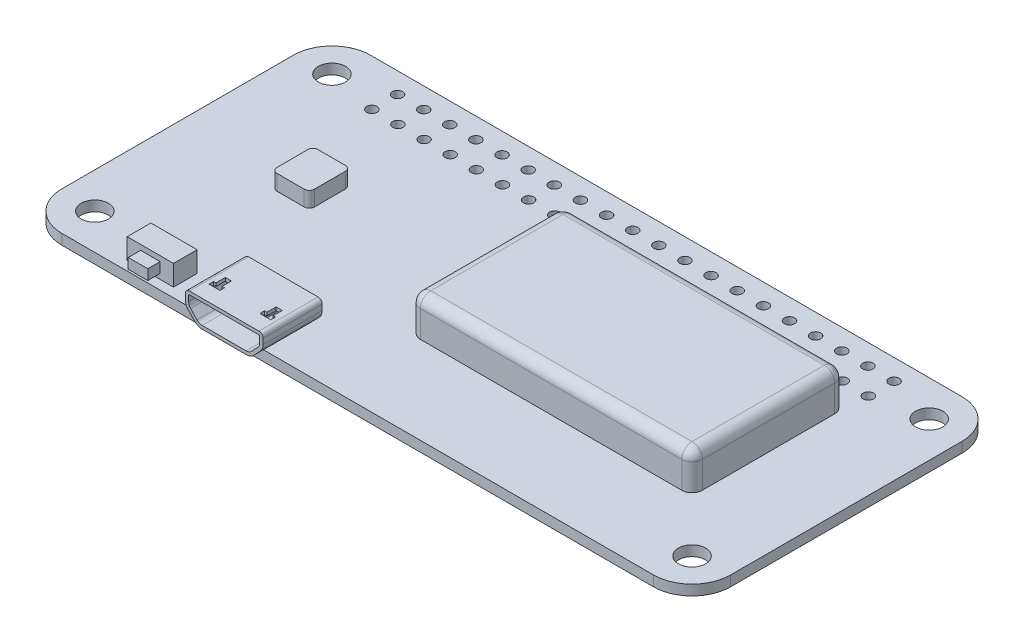
SolidWorks part; units mm, degrees
ref_plane "Front Plane" through (0, 0, 0) normal (0, 0, 1) x (1, 0, 0)
ref_plane "Top Plane" through (0, 0, 0) normal (0, 1, 0) x (1, 0, 0)
ref_plane "Right Plane" through (0, 0, 0) normal (1, 0, 0) x (0, 0, -1)
sketch "Sketch1" plane through (0, 0, 0) normal (0, 1, 0) x (1, 0, 0)
  line L1 (-28.75, 15) -> (28.75, 15)
  line L2 (-32.5, 11.25) -> (-32.5, -11.25)
  line L3 (-28.75, -15) -> (28.75, -15)
  line L4 (32.5, 11.25) -> (32.5, -11.25)
  line L5 (-32.5, 15) -> (32.5, -15) construction
  line L6 (-32.5, -15) -> (32.5, 15) construction
  arc A0 (-32.5, -11.25) -> (-28.75, -15) centre (-28.75, -11.25) ccw
  arc A1 (28.75, -15) -> (32.5, -11.25) centre (28.75, -11.25) ccw
  arc A2 (28.75, 15) -> (32.5, 11.25) centre (28.75, 11.25) cw
  arc A3 (-28.75, 15) -> (-32.5, 11.25) centre (-28.75, 11.25) ccw
  point P0 (0, 0)
  dimension "D3" = 3.75
  dimension "D1" = 65
  dimension "D2" = 30
extrude "Boss-Extrude1" add sketch "Sketch1" along normal blind 1 contours L1 A2 L4 A1 L3 A0 L2 A3
sketch "Sketch2" plane through (0, 1, 0) normal (0, 1, 0) x (1, 0, 0)
  line L0 (0, 15) -> (0, -15) construction
  line L1 (-28.75, 15) -> (28.75, 15) construction
  line L2 (-28.75, -15) -> (28.75, -15) construction
  line L3 (-32.5, 0) -> (32.5, 0) construction
  line L4 (-32.5, 11.25) -> (-32.5, -11.25) construction
  line L5 (32.5, 11.25) -> (32.5, -11.25) construction
  circle A0 centre (-29.025, 11.525) radius 1.325
  circle A2 centre (29.025, 11.525) radius 1.325
  circle A3 centre (29.025, -11.525) radius 1.325
  circle A4 centre (-29.025, -11.525) radius 1.325
  dimension "D1" = 2.65
  dimension "D2" = 2.15
  dimension "D3" = 2.15
extrude "Cut-Extrude1" cut sketch "Sketch2" against normal through all
sketch "Sketch3" plane through (0, 1, 0) normal (0, 1, 0) x (1, 0, 0)
  line L0 (-24.128, 13) -> (-24.128, 10.5) construction
  line L3 (-28.75, 15) -> (28.75, 15) construction
  line L5 (-32.5, 11.25) -> (-32.5, -11.25) construction
  circle A0 centre (-24.128, 13) radius 0.5
  circle A1 centre (-24.128, 10.5) radius 0.5
  dimension "D1" = 1
  dimension "D3" = 1.5
  dimension "D4" = 7.872
  dimension "D2" = 2.5
extrude "Cut-Extrude2" cut sketch "Sketch3" against normal through all
pattern_linear "LPattern1" count 20 spacing 2.54 along (1, 0, 0) of "Cut-Extrude2"
sketch "Sketch6" plane through (0, 1, 0) normal (0, 1, 0) x (1, 0, 0)
  line L0 (-28.75, -15) -> (28.75, -15) construction
  line L1 (-3.4, 8.35) -> (24, 8.35)
  line L2 (-3.4, 8.35) -> (-3.4, -6.5)
  line L3 (-3.4, -6.5) -> (24, -6.5)
  line L4 (24, 8.35) -> (24, -6.5)
  line L5 (-3.4, 8.35) -> (24, -6.5) construction
  line L6 (-3.4, -6.5) -> (24, 8.35) construction
  line L8 (32.5, 11.25) -> (32.5, -11.25) construction
  point P0 (10.3, 0.925)
  dimension "D1" = 27.4
  dimension "D2" = 8.5
  dimension "D3" = 8.5
  dimension "D4" = 14.85
sketch "Sketch15" plane through (0, 0, 15) normal (0, 0, 1) x (1, 0, 0)
  line L0 (-11.725, 1) -> (-11.725, 3.6) construction
  line L1 (-28.75, 1) -> (28.75, 1) construction
  line L2 (-15.1, 3.6) -> (-8.35, 3.6)
  line L3 (-7.95, 3.2) -> (-7.95, 2.6523)
  line L4 (-8.2286, 1.9598) -> (-8.8548, 1.3075)
  line L5 (-9.5762, 1) -> (-13.8738, 1)
  line L7 (-15.2214, 1.9598) -> (-14.5952, 1.3075)
  line L8 (-15.5, 3.2) -> (-15.5, 2.6523)
  line L9 (-32.5, 1) -> (-32.5, 0) construction
  arc A0 (-8.8548, 1.3075) -> (-9.5762, 1) centre (-9.5762, 2) cw
  arc A1 (-14.5952, 1.3075) -> (-13.8738, 1) centre (-13.8738, 2) ccw
  arc A2 (-7.95, 2.6523) -> (-8.2286, 1.9598) centre (-8.95, 2.6523) cw
  arc A3 (-15.2214, 1.9598) -> (-15.5, 2.6523) centre (-14.5, 2.6523) cw
  arc A4 (-8.35, 3.6) -> (-7.95, 3.2) centre (-8.35, 3.2) cw
  arc A5 (-15.5, 3.2) -> (-15.1, 3.6) centre (-15.1, 3.2) cw
  point P14 (-9.15, 1)
  point P17 (-14.3, 1)
  point P20 (-7.95, 2.25)
  point P23 (-15.5, 2.25)
  point P26 (-7.95, 3.6)
  point P29 (-15.5, 3.6)
  point P30 (-15.5, 2.9262)
  dimension "D6" = 1
  dimension "D7" = 0.4
  dimension "D1" = 7.55
  dimension "D2" = 2.6
  dimension "D3" = 1.35
  dimension "D4" = 5.15
  dimension "D5" = 17
extrude "Boss-Extrude6" add sketch "Sketch15" along normal blind 1.25 and the other way blind 4.5
sketch "Sketch16" plane through (0, 0, 16.25) normal (0, 0, 1) x (1, 0, 0)
  line L30 (-9.0857, 1.5291) -> (-8.4595, 2.1814)
  line L31 (-8.27, 2.6523) -> (-8.27, 3.2)
  line L32 (-8.35, 3.28) -> (-15.1, 3.28)
  line L33 (-15.18, 3.2) -> (-15.18, 2.6523)
  line L34 (-14.9905, 2.1814) -> (-14.3643, 1.5291)
  line L35 (-13.8738, 1.32) -> (-9.5762, 1.32)
  line L36 (-9.0857, 1.5291) -> (-8.4595, 2.1814)
  line L37 (-8.27, 2.6523) -> (-8.27, 3.2)
  line L38 (-8.35, 3.28) -> (-15.1, 3.28)
  line L39 (-15.18, 3.2) -> (-15.18, 2.6523)
  line L40 (-14.9905, 2.1814) -> (-14.3643, 1.5291)
  line L41 (-13.8738, 1.32) -> (-9.5762, 1.32)
  arc A30 (-9.5762, 1.32) -> (-9.0857, 1.5291) centre (-9.5762, 2) ccw
  arc A31 (-8.4595, 2.1814) -> (-8.27, 2.6523) centre (-8.95, 2.6523) ccw
  arc A32 (-8.27, 3.2) -> (-8.35, 3.28) centre (-8.35, 3.2) ccw
  arc A33 (-15.1, 3.28) -> (-15.18, 3.2) centre (-15.1, 3.2) ccw
  arc A34 (-15.18, 2.6523) -> (-14.9905, 2.1814) centre (-14.5, 2.6523) ccw
  arc A35 (-14.3643, 1.5291) -> (-13.8738, 1.32) centre (-13.8738, 2) ccw
  arc A36 (-9.5762, 1.32) -> (-9.0857, 1.5291) centre (-9.5762, 2) ccw
  arc A37 (-8.4595, 2.1814) -> (-8.27, 2.6523) centre (-8.95, 2.6523) ccw
  arc A38 (-8.27, 3.2) -> (-8.35, 3.28) centre (-8.35, 3.2) ccw
  arc A39 (-15.1, 3.28) -> (-15.18, 3.2) centre (-15.1, 3.2) ccw
  arc A40 (-15.18, 2.6523) -> (-14.9905, 2.1814) centre (-14.5, 2.6523) ccw
  arc A41 (-14.3643, 1.5291) -> (-13.8738, 1.32) centre (-13.8738, 2) ccw
  dimension "D2" = 0.32
extrude "Cut-Extrude9" cut sketch "Sketch16" against normal blind 5.25
sketch "Sketch17" plane through (0, 0, 11) normal (0, 0, 1) x (1, 0, 0)
  line L15 (-11.725, 1.32) -> (-11.725, 3.28) construction
  line L16 (-13.8738, 1.32) -> (-9.5762, 1.32) construction
  line L17 (-8.35, 3.28) -> (-15.1, 3.28) construction
  line L19 (-13.3, 2.52) -> (-10.15, 2.52)
  line L20 (-13.3, 2.52) -> (-13.3, 2.92)
  line L21 (-13.3, 2.92) -> (-10.15, 2.92)
  line L22 (-10.15, 2.52) -> (-10.15, 2.92)
  line L23 (-13.3, 2.52) -> (-10.15, 2.92) construction
  line L24 (-13.3, 2.92) -> (-10.15, 2.52) construction
  point P29 (-11.725, 2.72)
  dimension "D4" = 1.4
  dimension "D5" = 0.4
  dimension "D6" = 3.15
extrude "Boss-Extrude7" add sketch "Sketch17" along normal blind 3.5
sketch "Sketch18" plane through (0, 3.6, 0) normal (0, 1, 0) x (1, 0, 0)
  line L0 (-14.5, -13.37) -> (-14.5, -14.27)
  line L1 (-9.25, -13.37) -> (-9.25, -14.72) construction
  line L2 (-9.55, -13.37) -> (-9.55, -14.27)
  line L3 (-9.55, -14.27) -> (-9.775, -14.27)
  line L4 (-9.775, -14.27) -> (-9.775, -14.72)
  line L5 (-8.725, -14.27) -> (-8.725, -14.72)
  line L6 (-8.95, -14.27) -> (-8.725, -14.27)
  line L7 (-8.725, -14.72) -> (-9.775, -14.72)
  line L8 (-9.55, -13.37) -> (-8.95, -13.37)
  line L9 (-8.95, -13.37) -> (-8.95, -14.27)
  line L23 (-14.2, -13.37) -> (-14.2, -14.72) construction
  line L25 (-11.725, -16.25) -> (-11.725, -10.5) construction
  line L26 (-13.9, -13.37) -> (-14.5, -13.37)
  line L30 (-14.725, -14.72) -> (-13.675, -14.72)
  line L34 (-14.5, -14.27) -> (-14.725, -14.27)
  line L35 (-14.725, -14.27) -> (-14.725, -14.72)
  line L36 (-13.675, -14.27) -> (-13.675, -14.72)
  line L37 (-13.9, -14.27) -> (-13.675, -14.27)
  line L38 (-13.9, -13.37) -> (-13.9, -14.27)
  line L43 (-8.35, -16.25) -> (-15.1, -16.25) construction
  line L44 (-8.35, -10.5) -> (-15.1, -10.5) construction
  point P0 (0, 0)
  point P77 (-11.725, -16.25)
  point P80 (-11.725, -10.5)
  point P83 (-14.2, -14.72)
  point P85 (-14.2, -13.37)
  dimension "D7" = 1.53
  dimension "D8" = 1.05
  dimension "D9" = 0.6
  dimension "D10" = 1.35
  dimension "D11" = 0.9
  dimension "D13" = 2.475
extrude "Cut-Extrude10" cut sketch "Sketch18" against normal up to next
sketch "Sketch22" plane through (0, 1, 0) normal (0, 1, 0) x (1, 0, 0)
  line L1 (-22.35, 3) -> (-18.7, 3)
  line L2 (-22.35, 3) -> (-22.35, -1)
  line L3 (-22.35, -1) -> (-18.7, -1)
  line L4 (-18.7, 3) -> (-18.7, -1)
  line L5 (-28.75, 15) -> (28.75, 15) construction
  line L6 (-32.5, 11.25) -> (-32.5, -11.25) construction
  point P4 (-18.7, 1)
  dimension "D1" = 3.65
  dimension "D2" = 4
  dimension "D3" = 13.8
  dimension "D4" = 12
extrude "Boss-Extrude11" add sketch "Sketch22" along normal blind 1.5
fillet "Fillet5" radius 0.5 4 edges at (-18.7, 1.75, -3) (-22.35, 1.75, -3) (-18.7, 1.75, 1) (-22.35, 1.75, 1)
extrude "Boss-Extrude12" add sketch "Sketch6" along normal blind 3.6
fillet "Fillet4" radius 1 8 edges at (-3.4, 4.6, -0.925) (10.3, 4.6, 6.5) (24, 4.6, -0.925) (10.3, 4.6, -8.35) (-3.4, 2.8, -8.35) (24, 2.8, -8.35) (-3.4, 2.8, 6.5) (24, 2.8, 6.5)
sketch "Sketch23" plane through (0, 1, 0) normal (0, 1, 0) x (1, 0, 0)
  line L0 (-15.5, -10.5) -> (-15.5, -16.25) construction
  line L1 (-23.3, -11.8) -> (-18.8, -11.8)
  line L2 (-23.3, -11.8) -> (-23.3, -14.1)
  line L3 (-23.3, -14.1) -> (-18.8, -14.1)
  line L4 (-18.8, -11.8) -> (-18.8, -14.1)
  line L7 (-28.75, -15) -> (-13.8738, -15) construction
  dimension "D1" = 4.5
  dimension "D2" = 2.3
  dimension "D3" = 3.3
  dimension "D4" = 3.2
extrude "Boss-Extrude13" add sketch "Sketch23" along normal blind 2
sketch "Sketch24" plane through (0, 0, 14.1) normal (0, 0, 1) x (1, 0, 0)
  line L0 (-21.05, 3) -> (-21.05, 1) construction
  line L1 (-23.3, 3) -> (-18.8, 3) construction
  line L2 (-23.3, 1) -> (-18.8, 1) construction
  line L4 (-22, 2.5) -> (-20.1, 2.5)
  line L5 (-22, 2.5) -> (-22, 1.5)
  line L6 (-22, 1.5) -> (-20.1, 1.5)
  line L7 (-20.1, 2.5) -> (-20.1, 1.5)
  line L8 (-22, 2.5) -> (-20.1, 1.5) construction
  line L9 (-22, 1.5) -> (-20.1, 2.5) construction
  point P6 (-21.05, 2)
  point P11 (-22, 2)
  dimension "D1" = 1.9
  dimension "D2" = 1
extrude "Boss-Extrude14" add sketch "Sketch24" along normal blind 1.2
sketch "Sketch25" plane through (0, 0, 0) normal (0, -1, 0) x (1, 0, 0)
  line L0 (-28.75, 15) -> (28.75, 15) construction
  line L1 (-22.4, 12.1) -> (-19.1, 12.1)
  line L2 (-22.4, 12.1) -> (-22.4, 11.17)
  line L3 (-22.4, 11.17) -> (-19.1, 11.17)
  line L4 (-19.1, 12.1) -> (-19.1, 11.17)
  line L5 (-22.4, 9.6) -> (-19.1, 9.6)
  line L6 (-22.4, 9.6) -> (-22.4, 8.67)
  line L7 (-22.4, 8.67) -> (-19.1, 8.67)
  line L8 (-19.1, 9.6) -> (-19.1, 8.67)
  line L9 (-32.5, -11.25) -> (-32.5, 11.25) construction
  point P10 (-22.4, 9.135)
  dimension "D1" = 2.9
  dimension "D2" = 3.43
  dimension "D3" = 3.3
  dimension "D4" = 10.1
  dimension "D5" = 0.93
extrude "Boss-Extrude15" add sketch "Sketch25" along normal blind 1
fillet "Fillet6" radius 0.5 2 edges at (-19.1, -1, 9.135) (-19.1, -1, 11.635)
sketch "Sketch26" plane through (0, -1, 0) normal (0, -1, 0) x (1, 0, 0)
  line L0 (-22.4, 11.17) -> (-19.6, 11.17) construction
  line L1 (-22.1, 11.17) -> (-21.2, 11.17)
  line L2 (-22.1, 11.17) -> (-22.1, 12.1)
  line L3 (-22.1, 12.1) -> (-21.2, 12.1)
  line L4 (-21.2, 11.17) -> (-21.2, 12.1)
  line L5 (-19.6, 12.1) -> (-22.4, 12.1) construction
  line L6 (-22.4, 8.67) -> (-19.6, 8.67) construction
  line L7 (-22.1, 8.67) -> (-21.2, 8.67)
  line L8 (-22.1, 8.67) -> (-22.1, 9.6)
  line L9 (-22.1, 9.6) -> (-21.2, 9.6)
  line L10 (-21.2, 8.67) -> (-21.2, 9.6)
  line L11 (-19.6, 9.6) -> (-22.4, 9.6) construction
  line L12 (-22.4, 12.1) -> (-22.4, 11.17) construction
  dimension "D1" = 0.9
  dimension "D2" = 0.3
extrude "Boss-Extrude16" add sketch "Sketch26" along normal blind 0.7
fillet "Fillet7" radius 0.5 4 edges at (-22.1, -1.7, 11.635) (-21.2, -1.7, 11.635) (-22.1, -1.7, 9.135) (-21.2, -1.7, 9.135)
sketch "Sketch27" plane through (0, 0, 0) normal (0, -1, 0) x (1, 0, 0)
  line L0 (-29.5, 6.75) -> (-29.5, -6.75) construction
  line L1 (-30.5, 7.4) -> (-28.5, 7.4)
  line L2 (-30.5, 7.4) -> (-30.5, 6.1)
  line L3 (-30.5, 6.1) -> (-28.5, 6.1)
  line L4 (-28.5, 7.4) -> (-28.5, 6.1)
  line L5 (-30.5, 7.4) -> (-28.5, 6.1) construction
  line L6 (-30.5, 6.1) -> (-28.5, 7.4) construction
  line L7 (-30.5, 2.9) -> (-28.5, 2.9)
  line L8 (-30.5, 2.9) -> (-30.5, 1.6)
  line L9 (-30.5, 1.6) -> (-28.5, 1.6)
  line L10 (-28.5, 2.9) -> (-28.5, 1.6)
  line L11 (-30.5, 2.9) -> (-28.5, 1.6) construction
  line L12 (-30.5, 1.6) -> (-28.5, 2.9) construction
  line L13 (-30.5, -1.6) -> (-28.5, -1.6)
  line L14 (-30.5, -1.6) -> (-30.5, -2.9)
  line L15 (-30.5, -2.9) -> (-28.5, -2.9)
  line L16 (-28.5, -1.6) -> (-28.5, -2.9)
  line L17 (-30.5, -1.6) -> (-28.5, -2.9) construction
  line L18 (-30.5, -2.9) -> (-28.5, -1.6) construction
  line L19 (-30.5, -6.1) -> (-28.5, -6.1)
  line L20 (-30.5, -6.1) -> (-30.5, -7.4)
  line L21 (-30.5, -7.4) -> (-28.5, -7.4)
  line L22 (-28.5, -6.1) -> (-28.5, -7.4)
  line L23 (-30.5, -6.1) -> (-28.5, -7.4) construction
  line L24 (-30.5, -7.4) -> (-28.5, -6.1) construction
  line L25 (-29.5, 15) -> (-29.5, -15) construction
  line L26 (-28.75, 15) -> (28.75, 15) construction
  line L27 (-28.75, -15) -> (28.75, -15) construction
  line L28 (-32.5, -11.25) -> (-32.5, 11.25) construction
  point P0 (-29.5, 6.75)
  point P5 (-29.5, 2.25)
  point P10 (-29.5, -2.25)
  point P15 (-29.5, -6.75)
  point P22 (-29.5, 0)
  point P23 (-29.5, 0)
  point P24 (-25.596, -15)
  dimension "D1" = 13.5
  dimension "D2" = 1.3
  dimension "D3" = 4.5
  dimension "D4" = 4.5
  dimension "D5" = 2
  dimension "D6" = 4
extrude "Boss-Extrude17" add sketch "Sketch27" along normal blind 0.2
sketch "Sketch28" plane through (0, -0.2, 0) normal (0, -1, 0) x (1, 0, 0)
  line L0 (-29.5, 7.4) -> (-29.5, -7.4) construction
  line L1 (-28.5, 7.4) -> (-30.5, 7.4) construction
  line L2 (-30.5, -7.4) -> (-28.5, -7.4) construction
  line L3 (-28.5, 2.9) -> (-30.5, 2.9) construction
  line L4 (-28.9, 6.1) -> (-30.1, 6.1)
  line L5 (-28.9, 6.1) -> (-28.9, 7.4)
  line L6 (-28.9, 7.4) -> (-30.1, 7.4)
  line L7 (-30.1, 6.1) -> (-30.1, 7.4)
  line L8 (-28.9, 6.1) -> (-30.1, 7.4) construction
  line L9 (-28.9, 7.4) -> (-30.1, 6.1) construction
  line L10 (-28.9, 1.6) -> (-30.1, 1.6)
  line L11 (-28.9, 1.6) -> (-28.9, 2.9)
  line L12 (-28.9, 2.9) -> (-30.1, 2.9)
  line L13 (-30.1, 1.6) -> (-30.1, 2.9)
  line L14 (-28.9, 1.6) -> (-30.1, 2.9) construction
  line L15 (-28.9, 2.9) -> (-30.1, 1.6) construction
  line L16 (-28.5, -1.6) -> (-30.5, -1.6) construction
  line L17 (-28.9, -2.9) -> (-30.1, -2.9)
  line L18 (-28.9, -2.9) -> (-28.9, -1.6)
  line L19 (-28.9, -1.6) -> (-30.1, -1.6)
  line L20 (-30.1, -2.9) -> (-30.1, -1.6)
  line L21 (-28.9, -2.9) -> (-30.1, -1.6) construction
  line L22 (-28.9, -1.6) -> (-30.1, -2.9) construction
  line L23 (-28.5, -6.1) -> (-30.5, -6.1) construction
  line L24 (-28.9, -7.4) -> (-30.1, -7.4)
  line L25 (-28.9, -7.4) -> (-28.9, -6.1)
  line L26 (-28.9, -6.1) -> (-30.1, -6.1)
  line L27 (-30.1, -7.4) -> (-30.1, -6.1)
  line L28 (-28.9, -7.4) -> (-30.1, -6.1) construction
  line L29 (-28.9, -6.1) -> (-30.1, -7.4) construction
  line L30 (-30.5, -2.9) -> (-28.5, -2.9) construction
  line L31 (-30.5, 1.6) -> (-28.5, 1.6) construction
  line L32 (-30.5, 6.1) -> (-28.5, 6.1) construction
  point P6 (-29.5, 6.75)
  point P11 (-29.5, 2.25)
  point P18 (-29.5, -2.25)
  point P25 (-29.5, -6.75)
  dimension "D1" = 1.2
extrude "Boss-Extrude18" add sketch "Sketch28" along normal blind 0.6
